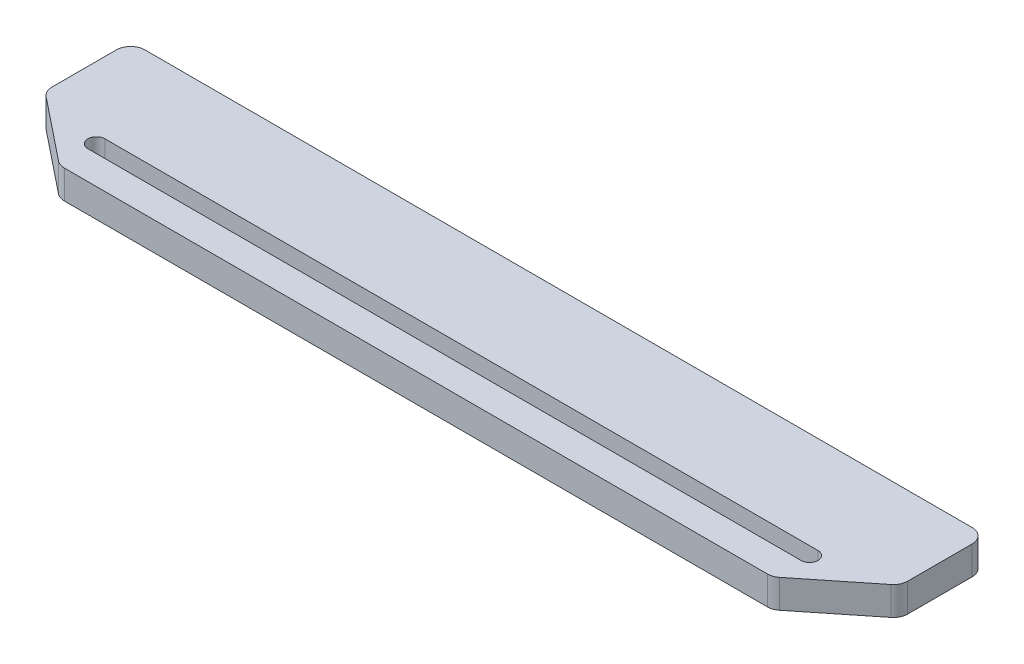
SolidWorks part; units mm, degrees
material "6061 Alloy"
ref_plane "Front Plane" through (0, 0, 0) normal (0, 0, 1) x (1, 0, 0)
ref_plane "Top Plane" through (0, 0, 0) normal (0, 1, 0) x (1, 0, 0)
ref_plane "Right Plane" through (0, 0, 0) normal (1, 0, 0) x (0, 0, -1)
sketch "Sketch1" plane through (0, 0, 0) normal (0, 1, 0) x (1, 0, 0)
  line L0 (0, -5) -> (0, -27.5969)
  line L3 (5, 0) -> (295, 0)
  line L5 (300, -5) -> (300, -27.5969)
  line L6 (1.8765, -31.5012) -> (23.6304, -48.9043)
  line L7 (26.7539, -50) -> (273.2461, -50)
  line L8 (276.3696, -48.9043) -> (298.1235, -31.5012)
  arc A0 (300, -5) -> (295, 0) centre (295, -5) ccw
  arc A1 (0, -5) -> (5, 0) centre (5, -5) cw
  arc A2 (23.6304, -48.9043) -> (26.7539, -50) centre (26.7539, -45) ccw
  arc A3 (276.3696, -48.9043) -> (273.2461, -50) centre (273.2461, -45) cw
  arc A4 (300, -27.5969) -> (298.1235, -31.5012) centre (295, -27.5969) cw
  arc A5 (1.8765, -31.5012) -> (0, -27.5969) centre (5, -27.5969) cw
  point P0 (0, 0)
  point P2 (150, 0)
  point P6 (150, -50)
  point P12 (300, 0)
  point P15 (0, 0)
  point P18 (25, -50)
  point P21 (275, -50)
  point P24 (300, -30)
  point P28 (0, -30)
  dimension "D5" = 5
  dimension "D6" = 5
  dimension "D1" = 300
  dimension "D2" = 250
  dimension "D3" = 30
  dimension "D4" = 20
extrude "Boss-Extrude1" add sketch "Sketch1" along normal blind 10
sketch "Sketch2" plane through (0, 0, 0) normal (0, 1, 0) x (1, 0, 0)
  line L0 (26.7539, -50) -> (273.2461, -50) construction
  line L1 (25, -37) -> (275, -37) construction
  line L2 (25, -34) -> (275, -34)
  line L3 (25, -40) -> (275, -40)
  line L6 (5, 0) -> (295, 0) construction
  line L7 (150, 0) -> (150, -60.0142) construction
  arc A0 (25, -34) -> (25, -40) centre (25, -37) ccw
  arc A1 (275, -40) -> (275, -34) centre (275, -37) ccw
  point P6 (150, -37)
  dimension "D1" = 6
  dimension "D2" = 250
  dimension "D3" = 10
extrude "Cut-Extrude4" cut sketch "Sketch2" against normal through all and the other way through all
